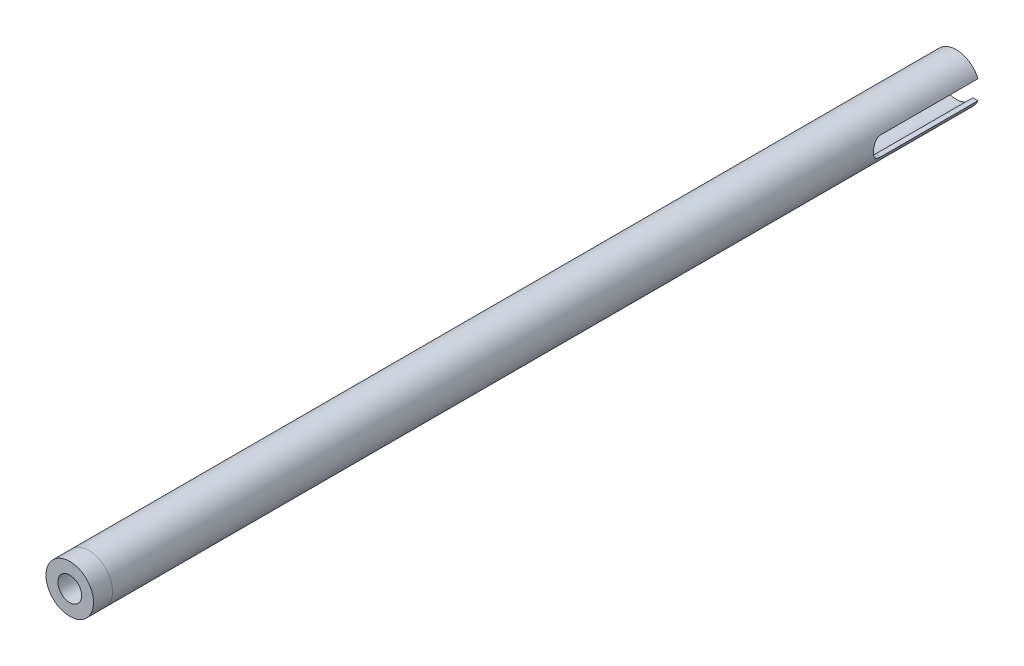
SolidWorks part; units mm, degrees
ref_plane "Front Plane" through (0, 0, 0) normal (0, 0, 1) x (1, 0, 0)
ref_plane "Top Plane" through (0, 0, 0) normal (0, 1, 0) x (1, 0, 0)
ref_plane "Right Plane" through (0, 0, 0) normal (1, 0, 0) x (0, 0, -1)
sketch "Axis" plane through (0, 0, 0) normal (0, 1, 0) x (1, 0, 0)
  line L0 (0, 0) -> (0, 295.5671) construction
  line L1 (0, 0) -> (0, -28.575) construction
  line L2 (0, 295.5671) -> (-7.9375, 295.5671) construction
  line L3 (0, 321.7609) -> (-28.3585, 228.1779) construction
  dimension "D1" = 28.575
  dimension "D2" = 7.9375
sketch "Sketch1" plane through (0, 0, 0) normal (0, 0, 1) x (1, 0, 0)
  line L0 (-7.9375, 0) -> (7.9375, 0) construction
  line L1 (-7.2748, 3.175) -> (7.2748, 3.175)
  line L2 (-7.2748, -3.175) -> (7.2748, -3.175)
  circle A0 centre (0, 0) radius 7.9375
  circle A1 centre (0, 0) radius 6.4135
  circle A2 centre (0, 0) radius 3.9688
  dimension "D1" = 15.875
  dimension "D3" = 7.9375
  dimension "D2" = 1.524
  dimension "D4" = 6.35
extrude "Threaded insert 1-1" add sketch "Sketch1" against normal blind 6.35 contours A2 L1 A1 | A1 L1 A0 | A2 L0 A1 L1 | A1 L0 A0 L1 | L0 A1 L2 A0 | L0 A2 L2 A1 | A2 L2 A1 | A1 L2 A0 | L0 A1 L2 A2 | L0 A0 L2 A1 | A0 L0 A1 L1 | A1 L0 A2 L1 region at (4.7887, 1.6543, 0) region at (4.7887, -1.6543, 0) region at (6.9234, 1.6163, 0) region at (6.9234, -1.6163, 0) region at (-4.7887, -1.6543, 0) region at (-4.7887, 1.6543, 0) region at (0, 4.6159, 0) region at (0, -4.6159, 0) region at (0, 6.5666, 0) region at (6.4237, -3.3281, 0) region at (-6.9234, -1.6163, 0) region at (-6.9234, 1.6163, 0)
extrude "Threaded insert 1-2" add sketch "Sketch1<3>" against normal blind 9.525 from surface contours A2 L1 A1 | A2 L0 A1 L1 | L0 A2 L2 A1 | A2 L2 A1 | L0 A1 L2 A2 | A1 L0 A2 L1 region at (4.7887, 1.6543, 0) region at (4.7887, -1.6543, 0) region at (-4.7887, -1.6543, 0) region at (-4.7887, 1.6543, 0) region at (0, 4.6159, 0) region at (0, -4.6159, 0) starting at face at (7.9375, 0, -6.35)
sketch "Sketch1<3>" plane through (0, 0, 0) normal (0, 0, 1) x (1, 0, 0) same geometry as "Sketch1"
extrude "A-arm tube" add sketch "Sketch1<4>" against normal up to vertex (295.5671 mm away) from surface separate body contours A1 L1 A0 | A1 L0 A0 L1 | L0 A1 L2 A0 | A1 L2 A0 | L0 A0 L2 A1 | A0 L0 A1 L1 region at (6.9234, 1.6163, 0) region at (6.9234, -1.6163, 0) region at (0, 6.5666, 0) region at (6.4237, -3.3281, 0) region at (-6.9234, -1.6163, 0) region at (-6.9234, 1.6163, 0) up to point (0, 0, -295.5671) starting at face at (6.4135, 0, -6.35)
sketch "Sketch1<4>" plane through (0, 0, 0) normal (0, 0, 1) x (1, 0, 0) same geometry as "Sketch1"
extrude "Apex slot" cut sketch "Sketch1<5>" along normal blind 35.56 from surface contours A0 L0 A1 L1 | L0 A0 L2 A1 | A1 L0 A0 L1 | L0 A1 L2 A0 region at (6.9234, 1.6163, 0) region at (6.9234, -1.6163, 0) region at (-6.9234, -1.6163, 0) region at (-6.9234, 1.6163, 0) starting at face at (6.4135, 0, -295.5671)
sketch "Sketch1<5>" plane through (0, 0, 0) normal (0, 0, 1) x (1, 0, 0) same geometry as "Sketch1"
fillet "Fillet1" radius 3.175 4 edges at (-6.4237, 3.175, -260.0071) (-6.4237, -3.175, -260.0071) (6.4237, -3.175, -260.0071) (6.4237, 3.175, -260.0071)
equation "\"tube diameter\"= 5 / 8"
equation "\"tube thickness\"= .06"
equation "\"apex thickness\"= .25"
equation "\"tube slot\"= 1.4"
equation "\"D1@Sketch1\"=\"tube diameter\""
equation "\"D2@Sketch1\"=\"tube thickness\""
equation "\"threaded insert hole\"= .3125"
equation "\"D3@Sketch1\"=\"threaded insert hole\""
equation "\"D4@Sketch1\"=\"apex thickness\""
equation "\"D1@Apex slot\" = \"tube slot\""
equation "\"D1@Fillet1\"=\"apex thickness\"/2"
equation "\"D2@Axis\"=\"tube diameter\"/2"
